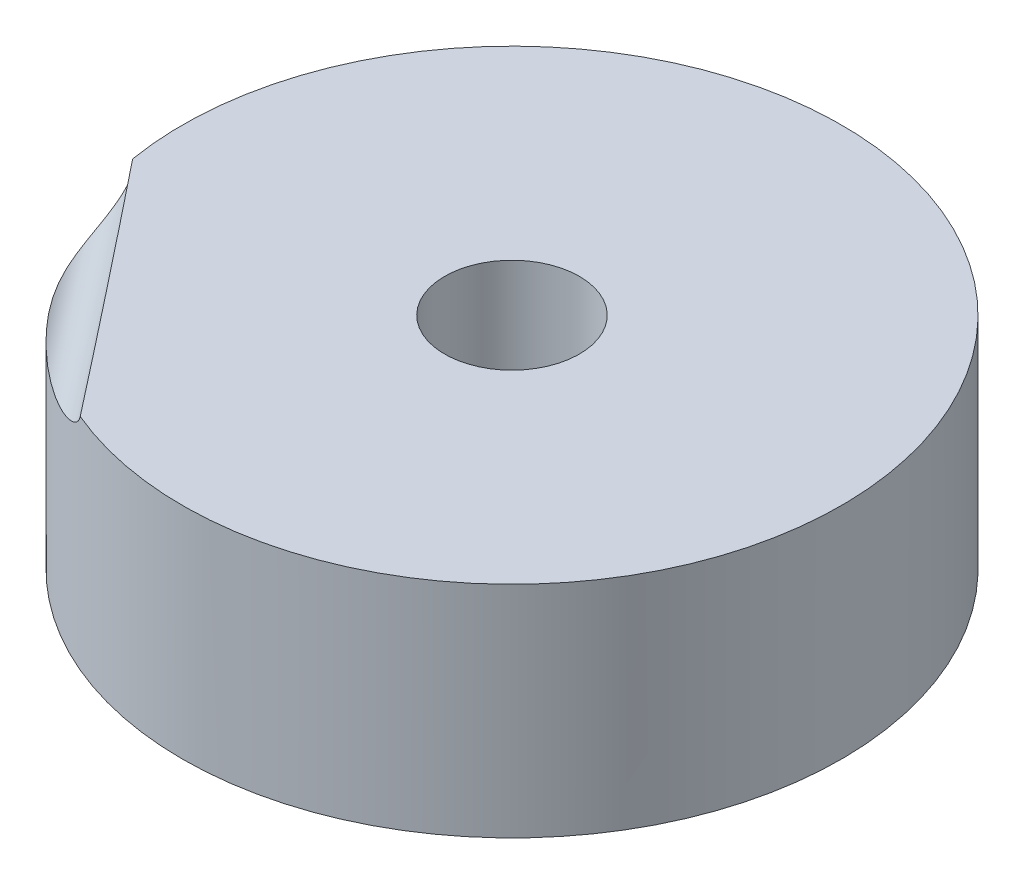
SolidWorks part; units mm, degrees
ref_plane "Front Plane" through (0, 0, 0) normal (0, 0, 1) x (1, 0, 0)
ref_plane "Top Plane" through (0, 0, 0) normal (0, 1, 0) x (1, 0, 0)
ref_plane "Right Plane" through (0, 0, 0) normal (1, 0, 0) x (0, 0, -1)
sketch "Sketch2" plane through (0, 0, 0) normal (0, 1, 0) x (1, 0, 0)
  circle A0 centre (0, 0) radius 28.575
  circle A1 centre (0, 0) radius 5.842
  dimension "D1" = 57.15
  dimension "D2" = 11.684
extrude "Boss-Extrude1" add sketch "Sketch2" along normal blind 19.05
extrude "Cut-Extrude1" cut sketch "Sketch3" against normal through all
sketch "Sketch3" plane through (-16.5456, 184.7521, -44.3525) normal (-0.619, -0.0319, -0.7847) x (-0.7851, 0.0006, 0.6193)
  circle A0 centre (41.7212, -167.1203) radius 2.3495
  circle A1 centre (44.0495, 14.2195) radius 2.3495
